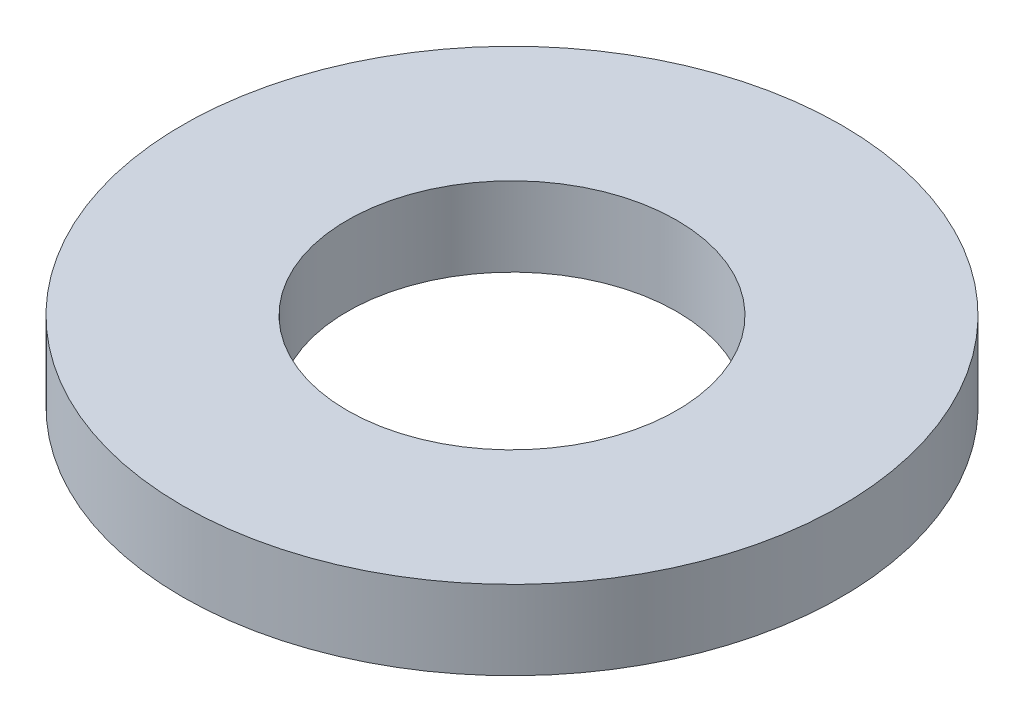
SolidWorks part; units mm, degrees
ref_plane "Front Plane" through (0, 0, 0) normal (0, 0, 1) x (1, 0, 0)
ref_plane "Top Plane" through (0, 0, 0) normal (0, 1, 0) x (1, 0, 0)
ref_plane "Right Plane" through (0, 0, 0) normal (1, 0, 0) x (0, 0, -1)
sketch "Sketch1" plane through (0, 0, 0) normal (0, 1, 0) x (1, 0, 0)
  circle A0 centre (0, 0) radius 25
  dimension "FLANGE_OD" = 50
extrude "Boss-Extrude1" add sketch "Sketch1" along normal blind 6
sketch "Sketch2" plane through (0, 0, 0) normal (0, 1, 0) x (1, 0, 0)
  circle A0 centre (0, 0) radius 12.5
  dimension "BORE_D" = 25
extrude "Cut-Extrude1" cut sketch "Sketch2" along normal through all
sketch "Sketch3" plane through (0, 6, 0) normal (0, 1, 0) x (1, 0, 0)
  circle A0 centre (0, 0) radius 10.4656 construction
  circle A1 centre (-10.4656, 0) radius 2.0316
  dimension "BOLT_D" = 4.0633
  dimension "BOLT_PCD" = 20.9313
extrude "Cut-Extrude2" cut sketch "Sketch3" against normal blind 4.6057 rebuild error yes
pattern_circular "CirPattern1" count 6 over 360 rebuild error yes
